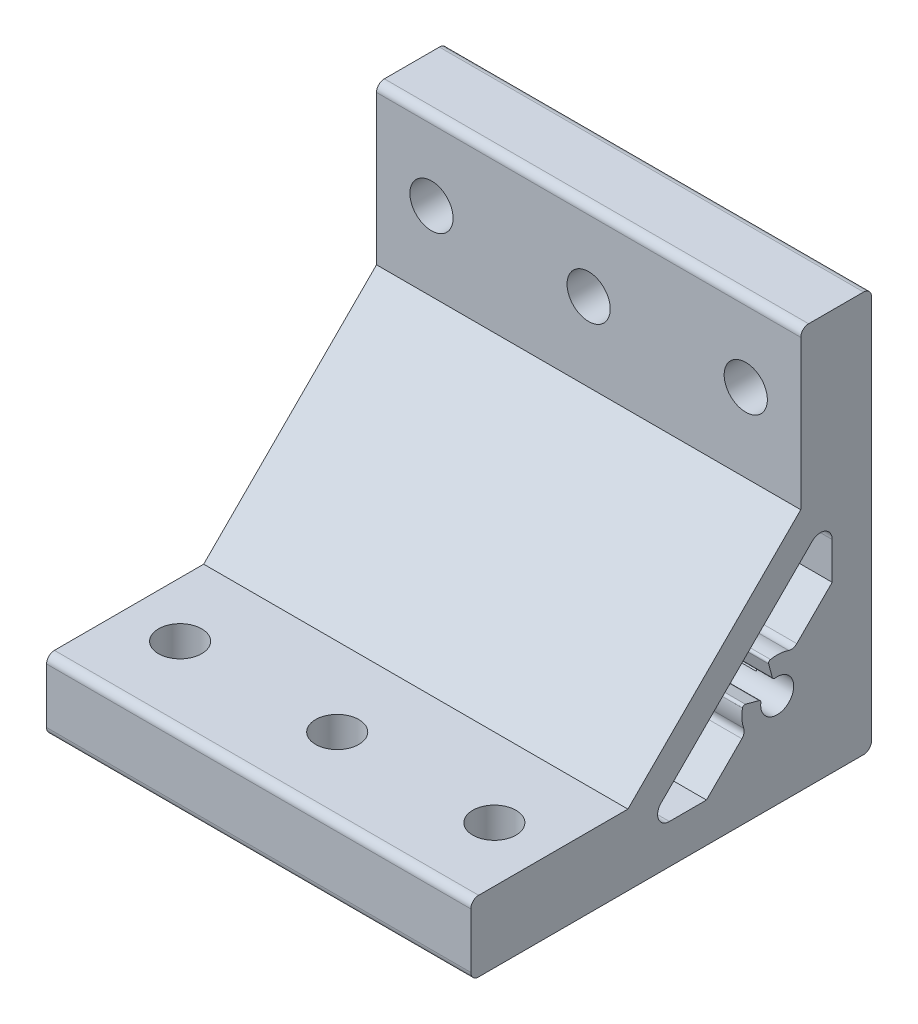
SolidWorks part; units mm, degrees
ref_plane "Front Plane" through (0, 0, 0) normal (0, 0, 1) x (1, 0, 0)
ref_plane "Top Plane" through (0, 0, 0) normal (0, 1, 0) x (1, 0, 0)
ref_plane "Right Plane" through (0, 0, 0) normal (1, 0, 0) x (0, 0, -1)
ref_plane "Plane1" through (0, 0, 0) normal (1, 0, 0) x (0, 0, -1)
sketch "Sketch1" plane through (0, 0, 0) normal (1, 0, 0) x (0, 0, -1)
  line L0 (-50, 0) -> (-1, 0)
  line L1 (0, 1) -> (0, 50)
  line L2 (-1, 51) -> (-8, 51)
  line L3 (-9, 50) -> (-9, 31)
  line L4 (-9, 31) -> (-31, 9)
  line L5 (-31, 9) -> (-50, 9)
  line L6 (-51, 8) -> (-51, 1)
  line L7 (-25.7218, 5) -> (-20.9993, 5)
  line L8 (-20.9993, 5) -> (-16.494, 9.5052)
  line L9 (-16.0465, 13.0843) -> (-14.3, 12.6163)
  line L10 (-12.6163, 14.3) -> (-13.0843, 16.0465)
  line L11 (-9.5052, 16.494) -> (-5, 20.9993)
  line L12 (-5, 20.9993) -> (-5, 25.7218)
  line L13 (-7.5607, 26.7825) -> (-26.7825, 7.5607)
  line L14 (-1, 0) -> (0, 0) construction
  line L15 (0, 0) -> (0, 1) construction
  line L16 (-1, 1) -> (-40.8569, 40.8569) construction
  arc A0 (-51, 1) -> (-50, 0) centre (-50, 1) ccw
  arc A1 (-1, 0) -> (0, 1) centre (-1, 1) ccw
  arc A2 (0, 50) -> (-1, 51) centre (-1, 50) ccw
  arc A3 (-8, 51) -> (-9, 50) centre (-8, 50) ccw
  arc A4 (-50, 9) -> (-51, 8) centre (-50, 8) ccw
  arc A5 (-26.7825, 7.5607) -> (-25.7218, 5) centre (-25.7218, 6.5) ccw
  arc A6 (-16.494, 9.5052) -> (-16.2556, 10.5372) centre (-17.2013, 10.2122) ccw
  arc A7 (-16.2556, 10.5372) -> (-16.4188, 12.8512) centre (-12, 12) cw
  arc A8 (-16.4188, 12.8512) -> (-16.0465, 13.0843) centre (-16.1242, 12.7945) cw
  arc A9 (-14.3, 12.6163) -> (-14.0805, 12.2857) centre (-14.3777, 12.3265) cw
  arc A10 (-14.0805, 12.2857) -> (-12.2857, 14.0805) centre (-12, 12) ccw
  arc A11 (-12.2857, 14.0805) -> (-12.6163, 14.3) centre (-12.3265, 14.3777) cw
  arc A12 (-13.0843, 16.0465) -> (-12.8512, 16.4188) centre (-12.7945, 16.1242) cw
  arc A13 (-12.8512, 16.4188) -> (-10.5377, 16.2558) centre (-12, 12) cw
  arc A14 (-10.5377, 16.2558) -> (-9.5052, 16.494) centre (-10.2122, 17.2013) ccw
  arc A15 (-5, 25.7218) -> (-7.5607, 26.7825) centre (-6.5, 25.7218) ccw
  dimension "D7" = 2.1
  dimension "D13" = 4.5
  dimension "D14" = 1
  dimension "D1" = 9
  dimension "D2" = 9
  dimension "D3" = 51
  dimension "D4" = 51
  dimension "D5" = 5
  dimension "D6" = 5
  dimension "D8" = 12
  dimension "D9" = 20
  dimension "D10" = 20
  dimension "D11" = 4
  dimension "D12" = 5.9
extrude "Boss-Extrude1" add sketch "Sketch1" against normal blind 27 and the other way blind 27
sketch "Sketch6" plane through (0, 0, 9) normal (0, 0, 1) x (1, 0, 0)
  line L0 (-20, 41) -> (20, 41) construction
  line L1 (0, 0) -> (0, 41) construction
  circle A0 centre (-20, 41) radius 2.75
  circle A1 centre (0, 41) radius 2.75
  circle A2 centre (20, 41) radius 2.75
  dimension "D3" = 5.5
  dimension "D1" = 20
  dimension "D2" = 41
extrude "Cut-Extrude5" cut sketch "Sketch6" against normal through all
sketch "Sketch7" plane through (0, 9, 0) normal (0, 1, 0) x (-1, 0, 0)
  line L0 (20, 41) -> (-20, 41) construction
  line L1 (0, 0) -> (0, 41) construction
  circle A0 centre (20, 41) radius 2.75
  circle A1 centre (0, 41) radius 2.75
  circle A2 centre (-20, 41) radius 2.75
  dimension "D2" = 5.5
  dimension "D1" = 41
  dimension "D3" = 20
extrude "Cut-Extrude6" cut sketch "Sketch7" against normal through all
sketch "Sketch9" plane through (0, 0, 0) normal (0, 0, -1) x (-1, 0, 0)
  circle A0 centre (20, 12) radius 2.4
  circle A1 centre (-20, 12) radius 2.4
  circle A2 centre (0, 12) radius 2.4
  circle A5 centre (20, 12) radius 2.75 construction
  circle A6 centre (-20, 12) radius 2.75 construction
  circle A7 centre (0, 12) radius 2.75 construction
  dimension "D1" = 4.8
extrude "Cut-Extrude7" cut sketch "Sketch9" against normal blind 10
